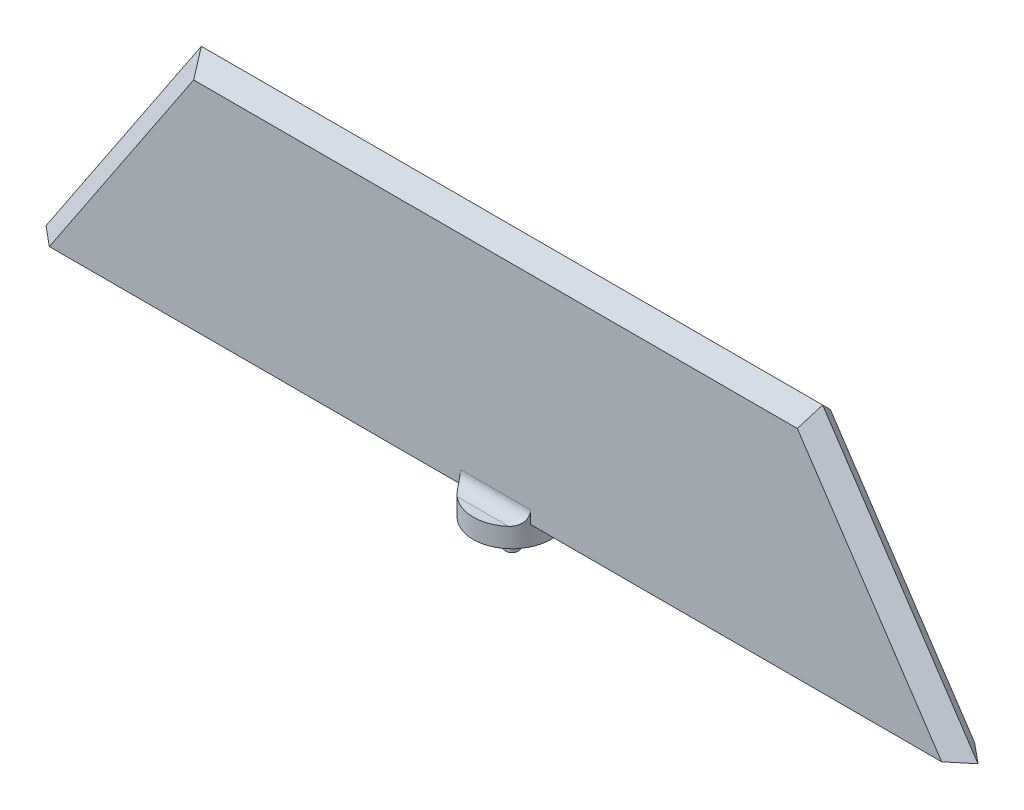
SolidWorks part; units mm, degrees
ref_plane "Alzado" through (0, 0, 0) normal (0, 0, 1) x (1, 0, 0)
ref_plane "Planta" through (0, 0, 0) normal (0, 1, 0) x (1, 0, 0)
ref_plane "Vista lateral" through (0, 0, 0) normal (1, 0, 0) x (0, 0, -1)
sketch "Croquis1" plane through (0, 0, 0) normal (0, 0, 1) x (1, 0, 0)
  line L0 (60, 0) -> (-60, 0)
  line L1 (-60, 0) -> (-40, 30)
  line L2 (-40, 30) -> (40, 30)
  line L3 (40, 30) -> (60, 0)
  point P4 (0, 0)
  dimension "D1" = 120
  dimension "D2" = 20
  dimension "3" = 30
  dimension "D3" = 20
extrude "Saliente-Extruir1" add sketch "Croquis1" along normal mid plane 4.25
sketch "Croquis2" plane through (0, 0, 0) normal (0, -1, 0) x (1, 0, 0)
  circle A0 centre (0, 0) radius 5
  dimension "D1" = 10
extrude "Saliente-Extruir2" add sketch "Croquis2" along normal blind 2.5
fillet "Redondeo1" radius 1.625 2 edges at (0, 0, -2.125) (0, 0, 2.125)
sketch "Sketch1" plane through (0, -2.5, 0) normal (0, -1, 0) x (1, 0, 0)
  circle A0 centre (0, 0) radius 2.45
  dimension "D1" = 4.9
extrude "Cut-Extrude1" cut sketch "Sketch1" against normal blind 3.1
chamfer "Chamfer1" distance 2.125 angle 45 6 edges at (50, 15, -2.125) (0, 30, -2.125) (-50, 15, -2.125) (50, 15, 2.125) (0, 30, 2.125) (-50, 15, 2.125)
sketch "Croquis3" plane through (0, 0.6, 0) normal (0, -1, 0) x (1, 0, 0)
  circle A0 centre (0, 0) radius 0.8
  dimension "D1" = 1.6
extrude "Saliente-Extruir3" add sketch "Croquis3" along normal blind 6.5
